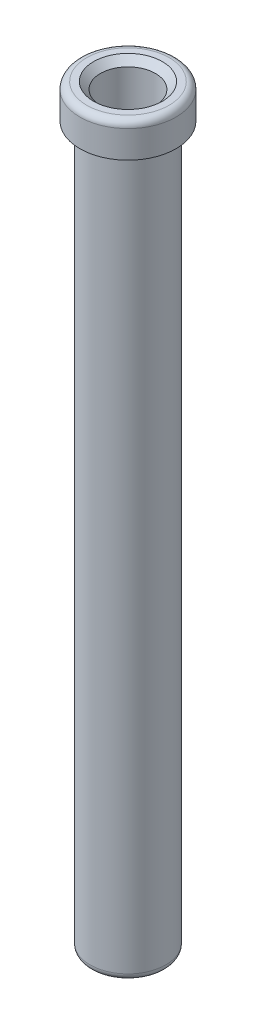
SolidWorks part; units mm, degrees
material "6061-T6 (SS)"
ref_plane "Front Plane" through (0, 0, 0) normal (0, 0, 1) x (1, 0, 0)
ref_plane "Top Plane" through (0, 0, 0) normal (0, 1, 0) x (1, 0, 0)
ref_plane "Right Plane" through (0, 0, 0) normal (1, 0, 0) x (0, 0, -1)
sketch "Sketch1" plane through (0, 0, 0) normal (0, 1, 0) x (1, 0, 0)
  circle A1 centre (0, 0) radius 2.8067
  dimension "D1" = 5.6134
extrude "Boss-Extrude1" add sketch "Sketch1" along normal blind 55.88
sketch "Sketch2" plane through (0, 55.88, 0) normal (0, 1, 0) x (1, 0, 0)
  point P0 (0, 0)
hole_wizard "#20 (0.161) Diameter Hole1" positions "3DSketch1" profile "Sketch4" hole size "#20" standard "ANSI Inch"
sketch3d "3DSketch1"
  point P0 (0, 55.88, 0)
sketch "Sketch4" plane through (0, 55.88, 0) normal (1, 0, 0) x (0, 0, 1)
  line L0 (0, 0) -> (0, 53.2986)
  line L1 (0, 53.2986) -> (2.0447, 52.07)
  line L2 (2.0447, 52.07) -> (2.0447, 0)
  line L5 (2.0447, 0) -> (0, 0)
  line L10 (0, 53.2986) -> (-2.0447, 52.07) construction
  line L11 (0, -6.35) -> (0, 107.95) construction
  dimension "Hole Dia." = 4.0894
  dimension "Hole Depth" = 52.07
  dimension "Drill Angle" = 118
sketch "Sketch5" plane through (0, 55.88, 0) normal (0, 1, 0) x (1, 0, 0)
  circle A1 centre (0, 0) radius 2.8067 construction
  circle A2 centre (0, 0) radius 3.5687
  circle A3 centre (0, 0) radius 3.5687
  circle A4 centre (0, 0) radius 2.8067
  dimension "D1" = 0.762
extrude "Boss-Extrude2" add sketch "Sketch5" against normal blind 2.54
chamfer "Chamfer1" distance 0.508 1 edges at (0, 55.88, 2.0447)
fillet "Fillet1" radius 0.508 1 edges at (0, 0, 2.8067)
fillet "Fillet2" radius 0.508 1 edges at (0, 55.88, 3.5687)
